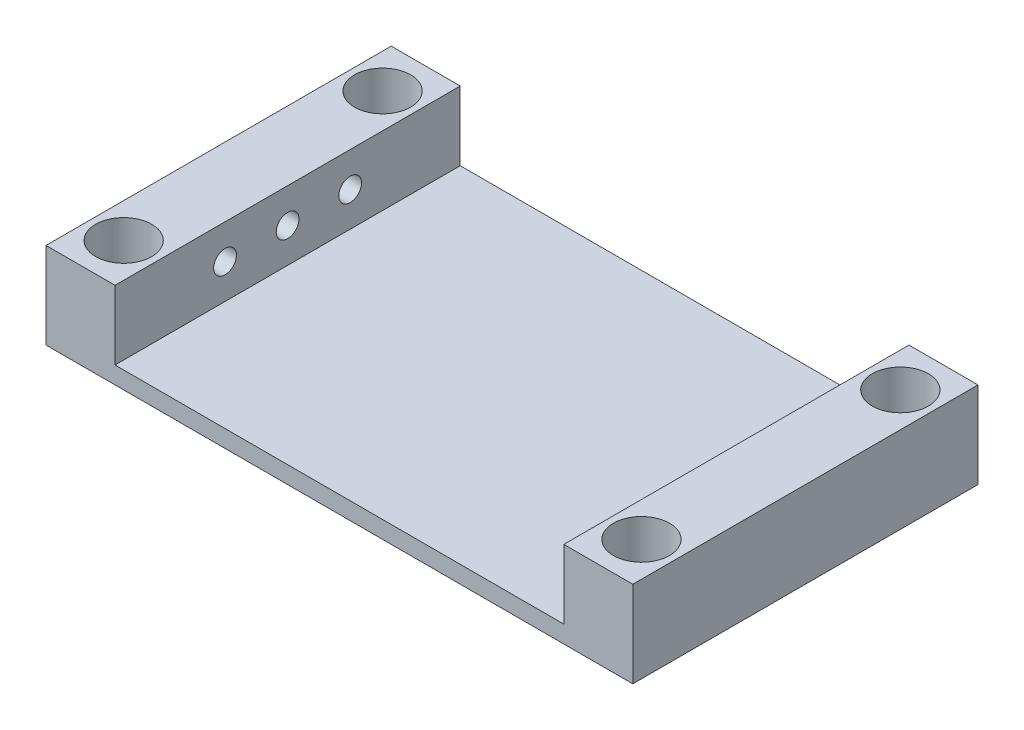
SolidWorks part; units mm, degrees
ref_plane "Front Plane" through (0, 0, 0) normal (0, 0, 1) x (1, 0, 0)
ref_plane "Top Plane" through (0, 0, 0) normal (0, 1, 0) x (1, 0, 0)
ref_plane "Right Plane" through (0, 0, 0) normal (1, 0, 0) x (0, 0, -1)
sketch "Sketch1" plane through (0, 0, 0) normal (0, 0, 1) x (1, 0, 0)
  line L0 (-68, 0) -> (-68, 10)
  line L1 (0, 0) -> (-68, 0)
  line L2 (-68, 10) -> (-60, 10)
  line L3 (-60, 10) -> (-60, 2)
  line L4 (-60, 2) -> (-8, 2)
  line L5 (-8, 2) -> (-8, 10)
  line L6 (-8, 10) -> (0, 10)
  line L7 (0, 10) -> (0, 0)
  dimension "D1" = 52
  dimension "D2" = 8
  dimension "D3" = 8
  dimension "D4" = 10
extrude "Boss-Extrude1" add sketch "Sketch1" along normal blind 40
sketch "Sketch3" plane through (0, 10, 0) normal (0, 1, 0) x (1, 0, 0)
  line L0 (-64, 0) -> (-64, -50000) construction
  line L1 (-60, 0) -> (-68, 0) construction
  line L2 (-4, 0) -> (-4, -50000) construction
  line L3 (0, 0) -> (-8, 0) construction
  line L4 (-64.8967, -5) -> (49935.1033, -5) construction
  line L5 (-66, -35) -> (49934, -35) construction
  line L6 (-60, -40) -> (-68, -40) construction
  circle A0 centre (-64, -5) radius 3.25
  circle A1 centre (-4, -5) radius 3.25
  circle A2 centre (-4, -35) radius 3.25
  circle A3 centre (-64, -35) radius 3.25
  point P4 (-64, 0)
  point P9 (-4, 0)
  dimension "D1" = 6.5
  dimension "D5" = 30
  dimension "D6" = 5
  dimension "D7" = 5
  dimension "D2" = 2
  dimension "D3" = 2
extrude "Cut-Extrude1" cut sketch "Sketch3" against normal blind 8
sketch "Sketch4" plane through (0, 0, 0) normal (0, -1, 0) x (1, 0, 0)
  circle A0 centre (-64, 35) radius 2
  circle A1 centre (-4, 35) radius 2
  circle A2 centre (-4, 5) radius 2
  circle A3 centre (-64, 5) radius 2
  circle A4 centre (-4, 35) radius 3.25 construction
  dimension "D1" = 4
  dimension "D2" = 2
  dimension "D3" = 2
extrude "Cut-Extrude2" cut sketch "Sketch4" against normal blind 8
sketch "Sketch5" plane through (-68, 0, 0) normal (-1, 0, 0) x (0, 0, 1)
  line L0 (1.75, 6) -> (50001.75, 6) construction
  line L1 (31.75, 10) -> (31.75, 2) construction
  line L2 (1.75, 10) -> (1.75, 2) construction
  line L3 (8.25, 2) -> (8.25, 10) construction
  circle A0 centre (12.75, 6) radius 1.32
  circle A1 centre (20, 6) radius 1.32
  circle A2 centre (27.25, 6) radius 1.32
  point P8 (1.75, 6)
  dimension "D1" = 2.64
  dimension "D4" = 4.5
  dimension "D2" = 4.5
  dimension "D3" = 3
extrude "Cut-Extrude3" cut sketch "Sketch5" against normal up to next
sketch "Sketch6" plane through (-68, 0, 0) normal (-1, 0, 0) x (0, 0, 1)
  circle A0 centre (12.75, 6) radius 3.25
  circle A1 centre (20, 6) radius 3.25
  circle A2 centre (27.25, 6) radius 3.25
  circle A3 centre (20, 6) radius 1.32 construction
  dimension "D1" = 6.5
  dimension "D2" = 3
extrude "Cut-Extrude4" cut sketch "Sketch6" against normal blind 6
